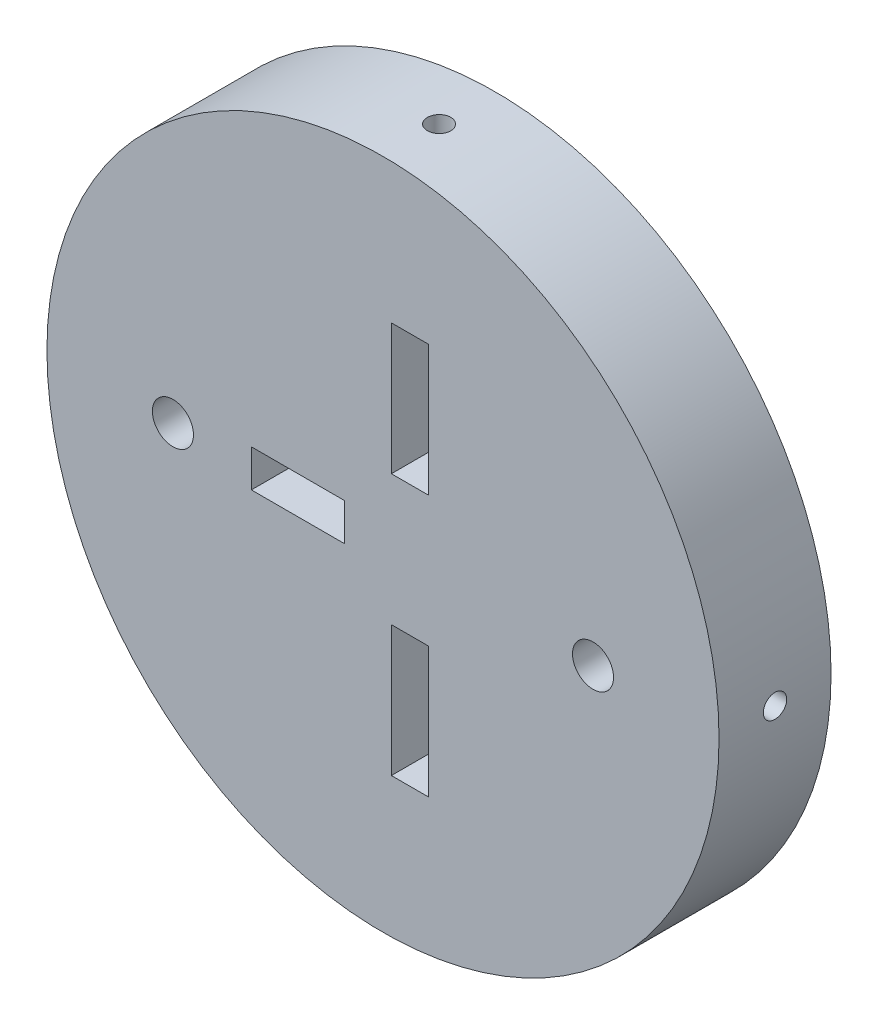
SolidWorks part; units mm, degrees
material "Beech"
ref_plane "Front Plane" through (0, 0, 0) normal (0, 0, 1) x (1, 0, 0)
ref_plane "Top Plane" through (0, 0, 0) normal (0, 1, 0) x (1, 0, 0)
ref_plane "Right Plane" through (0, 0, 0) normal (1, 0, 0) x (0, 0, -1)
sketch "Sketch1" plane through (0, 0, 0) normal (0, 0, 1) x (1, 0, 0)
  circle A0 centre (0, 0) radius 45.72
  dimension "D1" = 91.44
extrude "Boss-Extrude1" add sketch "Sketch1" along normal blind 15.24
sketch "Sketch2" plane through (0, 0, 15.24) normal (0, 0, 1) x (1, 0, 0)
  circle A0 centre (-28.575, 0) radius 2.794
  circle A1 centre (28.575, 0) radius 2.794
  point P4 (0, 0)
  dimension "D1" = 5.588
  dimension "D2" = 5.588
  dimension "D3" = 28.575
  dimension "D4" = 28.575
extrude "Cut-Extrude1" cut sketch "Sketch2" against normal through all
sketch "Sketch3" plane through (0, 0, 0) normal (0, 1, 0) x (1, 0, 0)
  circle A0 centre (0, -7.62) radius 1.5875
  point P2 (0, 0)
  dimension "D2" = 3.175
  dimension "D1" = 7.62
extrude "Cut-Extrude2" cut sketch "Sketch3" along normal blind 15.24 from offset 38.1
ref_axis "Axis1" through (0, 0, 15.24) along (0, 0, -1)
pattern_circular "CirPattern1" count 4 every 90 about axis through (0, 0, 15.24) along (0, 0, -1) of "Cut-Extrude2"
sketch "Sketch4" plane through (0, 0, 15.24) normal (0, 0, 1) x (1, 0, 0)
  line L0 (6.2227, 26.67) -> (6.2227, 44.45) construction
  line L1 (1.1427, 26.67) -> (6.2227, 26.67)
  line L2 (1.1427, 26.67) -> (1.1427, 8.89)
  line L3 (1.1427, 8.89) -> (6.2227, 8.89)
  line L4 (6.2227, 26.67) -> (6.2227, 8.89)
  line L5 (1.1427, -8.89) -> (6.2227, -8.89)
  line L6 (1.1427, -8.89) -> (1.1427, -26.67)
  line L7 (1.1427, -26.67) -> (6.2227, -26.67)
  line L8 (6.2227, -8.89) -> (6.2227, -26.67)
  line L9 (6.2227, 8.89) -> (6.2227, -8.89) construction
  line L10 (6.2227, -26.67) -> (6.2227, -44.45) construction
  line L12 (6.2227, -38.1) -> (25.2727, -38.1) construction
  line L13 (6.2227, -38.1) -> (6.2227, 38.1) construction
  line L14 (6.2227, 38.1) -> (25.2727, 38.1) construction
  line L15 (25.2727, -38.1) -> (25.2727, 38.1) construction
  line L16 (-17.9073, -2.54) -> (-5.2073, -2.54)
  line L17 (-17.9073, -2.54) -> (-17.9073, 2.54)
  line L18 (-17.9073, 2.54) -> (-5.2073, 2.54)
  line L19 (-5.2073, -2.54) -> (-5.2073, 2.54)
  line L20 (-17.9073, -2.54) -> (-5.2073, 2.54) construction
  line L21 (-17.9073, 2.54) -> (-5.2073, -2.54) construction
  circle A0 centre (0, 0) radius 45.72 construction
  point P8 (0, 0)
  point P17 (-11.5573, 0)
  point P22 (0, 0)
  point P24 (6.2227, -42.2087)
  point P25 (6.2227, 0)
  dimension "D1" = 5.08
  dimension "D2" = 19.05
  dimension "D3" = 76.2
  dimension "D4" = 12.7
  dimension "D5" = 5.08
  dimension "D6" = 6.35
  dimension "D7" = 88.9
extrude "Cut-Extrude3" cut sketch "Sketch4" against normal through all
